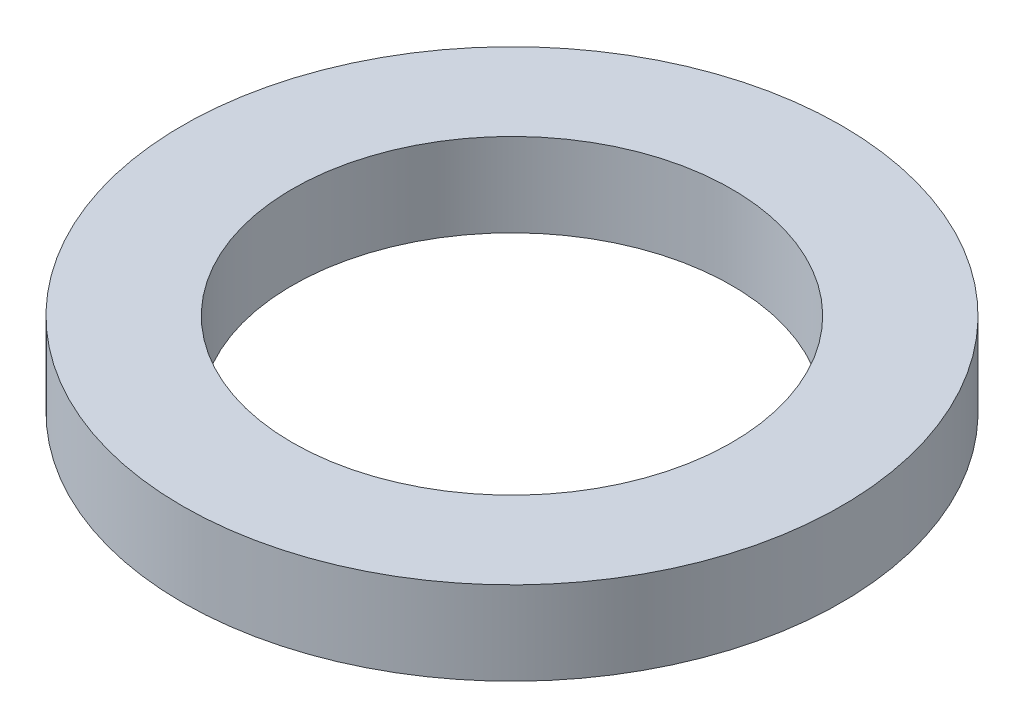
SolidWorks part; units mm, degrees
ref_plane "Front Plane" through (0, 0, 0) normal (0, 0, 1) x (1, 0, 0)
ref_plane "Top Plane" through (0, 0, 0) normal (0, 1, 0) x (1, 0, 0)
ref_plane "Right Plane" through (0, 0, 0) normal (1, 0, 0) x (0, 0, -1)
sketch "Sketch1" plane through (0, 0, 0) normal (0, 1, 0) x (1, 0, 0)
  circle A0 centre (0, 0) radius 75
  dimension "FLANGE_OD" = 150
extrude "Boss-Extrude1" add sketch "Sketch1" along normal blind 19
sketch "Sketch2" plane through (0, 0, 0) normal (0, 1, 0) x (1, 0, 0)
  circle A0 centre (0, 0) radius 50
  dimension "BORE_D" = 100
extrude "Cut-Extrude1" cut sketch "Sketch2" along normal through all
sketch "Sketch3" plane through (0, 19, 0) normal (0, 1, 0) x (1, 0, 0)
  circle A0 centre (0, 0) radius 27.2763 construction
  circle A1 centre (-27.2763, 0) radius 2.9098
  dimension "BOLT_D" = 5.8196
  dimension "BOLT_PCD" = 54.5526
extrude "Cut-Extrude2" cut sketch "Sketch3" against normal blind 15.1503 rebuild error yes
pattern_circular "CirPattern1" count 8 over 360 rebuild error yes
